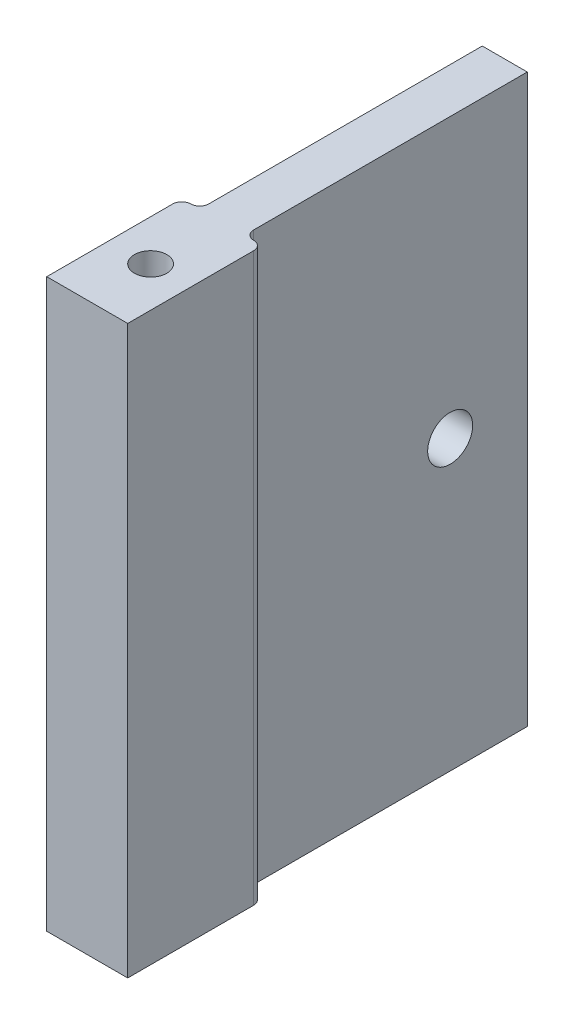
SolidWorks part; units mm, degrees
ref_plane "Plan de face" through (0, 0, 0) normal (0, 0, 1) x (1, 0, 0)
ref_plane "Plan de dessus" through (0, 0, 0) normal (0, 1, 0) x (1, 0, 0)
ref_plane "Plan de droite" through (0, 0, 0) normal (1, 0, 0) x (0, 0, -1)
sketch "Esquisse1" plane through (0, 0, 0) normal (0, 0, 1) x (1, 0, 0)
  line L1 (-14.0429, 20.9356) -> (-5.0429, 20.9356)
  line L2 (-14.0429, 20.9356) -> (-14.0429, -42.0644)
  line L3 (-14.0429, -42.0644) -> (-5.0429, -42.0644)
  line L4 (-5.0429, 20.9356) -> (-5.0429, -42.0644)
  dimension "D1" = 63
  dimension "D2" = 9
extrude "Boss.-Extru.1" add sketch "Esquisse1" along normal blind 10
sketch "Esquisse2" plane through (0, 0, 0) normal (0, 0, -1) x (-1, 0, 0)
  line L0 (5.0429, 20.9356) -> (14.0429, 20.9356) construction
  line L1 (7.0429, 20.9356) -> (12.0429, 20.9356)
  line L2 (7.0429, 20.9356) -> (7.0429, -42.0644)
  line L3 (7.0429, -42.0644) -> (12.0429, -42.0644)
  line L4 (12.0429, 20.9356) -> (12.0429, -42.0644)
  line L5 (14.0429, -42.0644) -> (5.0429, -42.0644) construction
  line L6 (14.0429, 20.9356) -> (14.0429, -42.0644) construction
  line L7 (5.0429, -42.0644) -> (5.0429, 20.9356) construction
  dimension "D1" = 2
  dimension "D2" = 2
  dimension "D3" = 5
extrude "Boss.-Extru.2" add sketch "Esquisse2" along normal blind 63
fillet "Congé3" radius 1 1 edges at (-7.0429, -10.5644, 0) type face fillet first side face at (-6.0429, -10.5644, 0) second side face at (-7.0429, -10.5644, -31.5)
fillet "Congé4" radius 1 1 edges at (-12.0429, -10.5644, 0) type face fillet first side face at (-13.0429, -10.5644, 0) second side face at (-12.0429, -10.5644, -31.5)
fillet "Congé5" radius 1 1 edges at (-5.0429, -10.5644, 0) type face fillet first side face at (-5.0429, -10.5644, 5) second side face at (-5.5429, -10.5644, 0)
fillet "Congé6" radius 1 1 edges at (-14.0429, -10.5644, 0) type face fillet first side face at (-14.0429, -10.5644, 5) second side face at (-13.5429, -10.5644, 0)
sketch "Esquisse3" plane through (-12.0429, 0, 0) normal (-1, 0, 0) x (0, 0, 1)
  line L0 (-63, -42.0644) -> (-1, -42.0644) construction
  line L1 (-63, -42.0644) -> (-63, 20.9356) construction
  circle A0 centre (-43, -10.5644) radius 2.5
  dimension "D1" = 31.5
  dimension "D2" = 20
extrude "Enlèv. mat.-Extru.1" cut sketch "Esquisse3" against normal through all
sketch "Esquisse7" plane through (-7.0429, 0, 0) normal (1, 0, 0) x (0, 0, -1)
  line L0 (51.2484, 20.9356) -> (51.2484, -42.8394)
  line L1 (63, 20.9356) -> (1, 20.9356) construction
extrude "Enlèv. mat.-Extru.3" cut sketch "Esquisse7" against normal through all and the other way through all contours L0
sketch "Esquisse8" plane through (-7.0429, 0, 0) normal (1, 0, 0) x (0, 0, -1)
  line L0 (31.4026, 24.1015) -> (31.4026, -47.7427)
  line L1 (31.4026, -47.7427) -> (31.4026, 24.1015)
  line L3 (31.4026, -47.7427) -> (31.4026, 24.1015)
ref_plane "Plan1" through (0, 0, -31.4026) normal (0, 0, 1) x (0, -1, 0)
split "Fractionner1" trim tools "Plan1" bodies to split 104 resulting bodies 106 107
delete or keep bodies "Corps-Supprimer/Garder 1" type delete bodies bodies 107
sketch "Esquisse9" plane through (-7.0429, 0, 0) normal (1, 0, 0) x (0, 0, -1)
  circle A0 centre (22.8353, -10.0364) radius 2.5
extrude "Enlèv. mat.-Extru.4" cut sketch "Esquisse9" against normal blind 23
sketch "Esquisse12" plane through (0, 0, 10) normal (0, 0, 1) x (1, 0, 0)
  line L1 (-14.0429, 20.9356) -> (-5.0429, 20.9356)
  line L2 (-14.0429, 20.9356) -> (-14.0429, -42.0644)
  line L3 (-14.0429, -42.0644) -> (-5.0429, -42.0644)
  line L4 (-5.0429, 20.9356) -> (-5.0429, -42.0644)
extrude "Boss.-Extru.4" add sketch "Esquisse12" along normal blind 5
sketch "Esquisse13" plane through (0, 20.9356, 0) normal (0, 1, 0) x (1, 0, 0)
  circle A0 centre (-9.5, -8) radius 1.8
extrude "Enlèv. mat.-Extru.6" cut sketch "Esquisse13" against normal blind 4
sketch "Esquisse14" plane through (0, -42.0644, 0) normal (0, -1, 0) x (-1, 0, 0)
  circle A0 centre (9.5, -8) radius 1.8
extrude "Enlèv. mat.-Extru.7" cut sketch "Esquisse14" against normal blind 4
